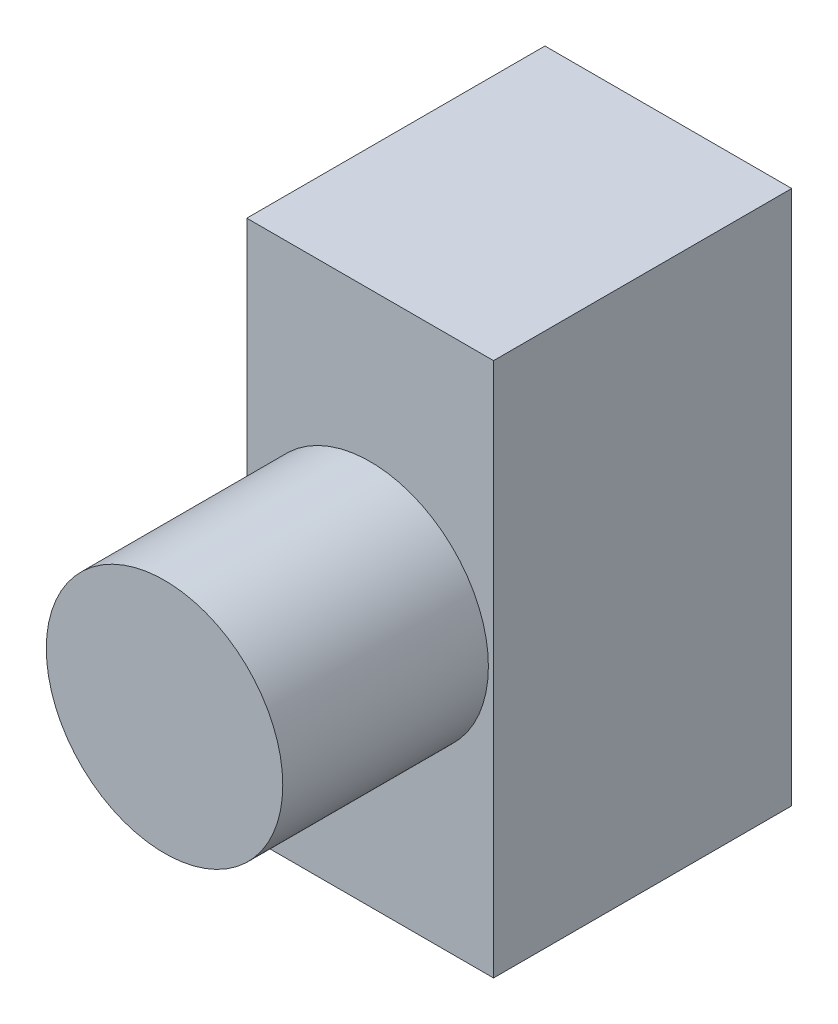
SolidWorks part; units mm, degrees
ref_plane "Front Plane" through (0, 0, 0) normal (0, 0, 1) x (1, 0, 0)
ref_plane "Top Plane" through (0, 0, 0) normal (0, 1, 0) x (1, 0, 0)
ref_plane "Right Plane" through (0, 0, 0) normal (1, 0, 0) x (0, 0, -1)
ref_axis "X" through (-88.99, 0, 0) along (1, 0, 0)
ref_axis "Y" through (0, 55, 0) along (0, -1, 0)
ref_axis "Z" through (0, 0, -88.99) along (0, 0, 1)
sketch "Sketch1" plane through (0, 0, 0) normal (0, 0, 1) x (1, 0, 0)
  line L1 (-6, 13) -> (6, 13)
  line L2 (-6, 13) -> (-6, -13)
  line L3 (-6, -13) -> (6, -13)
  line L4 (6, 13) -> (6, -13)
  line L5 (-6, 13) -> (6, -13) construction
  line L6 (-6, -13) -> (6, 13) construction
  circle A0 centre (0, 0) radius 5.75
  point P0 (0, 0)
  dimension "D3" = 11.5
  dimension "D1" = 26
  dimension "D2" = 12
extrude "Boss-Extrude1" add sketch "Sketch1" against normal blind 14.5 contours L4 L3 L2 L1
extrude "Boss-Extrude2" add sketch "Sketch1<3>" along normal blind 10 contours A0 region at (0, 0, 0)
sketch "Sketch1<3>" plane through (0, 0, 0) normal (0, 0, 1) x (1, 0, 0) same geometry as "Sketch1"
